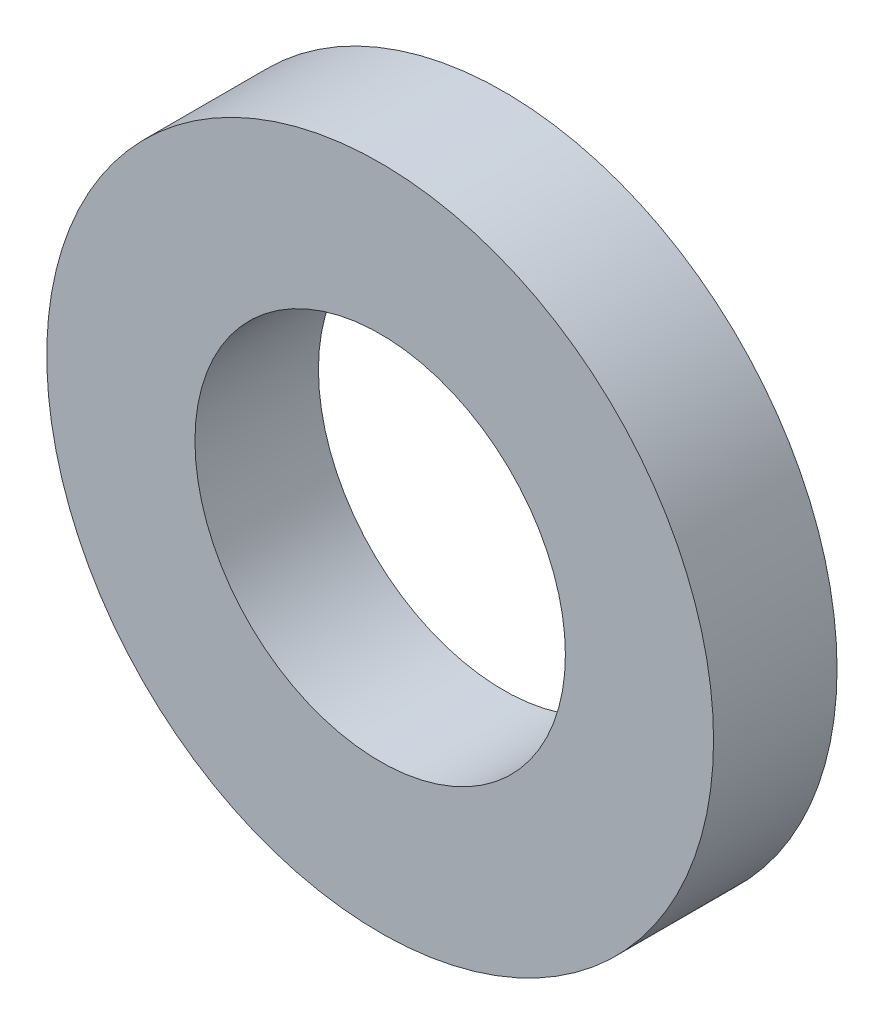
SolidWorks part; units mm, degrees
ref_plane "Front Plane" through (0, 0, 0) normal (0, 0, 1) x (1, 0, 0)
ref_plane "Top Plane" through (0, 0, 0) normal (0, 1, 0) x (1, 0, 0)
ref_plane "Right Plane" through (0, 0, 0) normal (1, 0, 0) x (0, 0, -1)
sketch "Sketch1" plane through (0, 0, 0) normal (0, 0, 1) x (1, 0, 0)
  circle A0 centre (0, 0) radius 13.5
  circle A1 centre (0, 0) radius 7.5
  dimension "D1" = 27
  dimension "D2" = 15
extrude "Boss-Extrude1" add sketch "Sketch1" along normal blind 5
